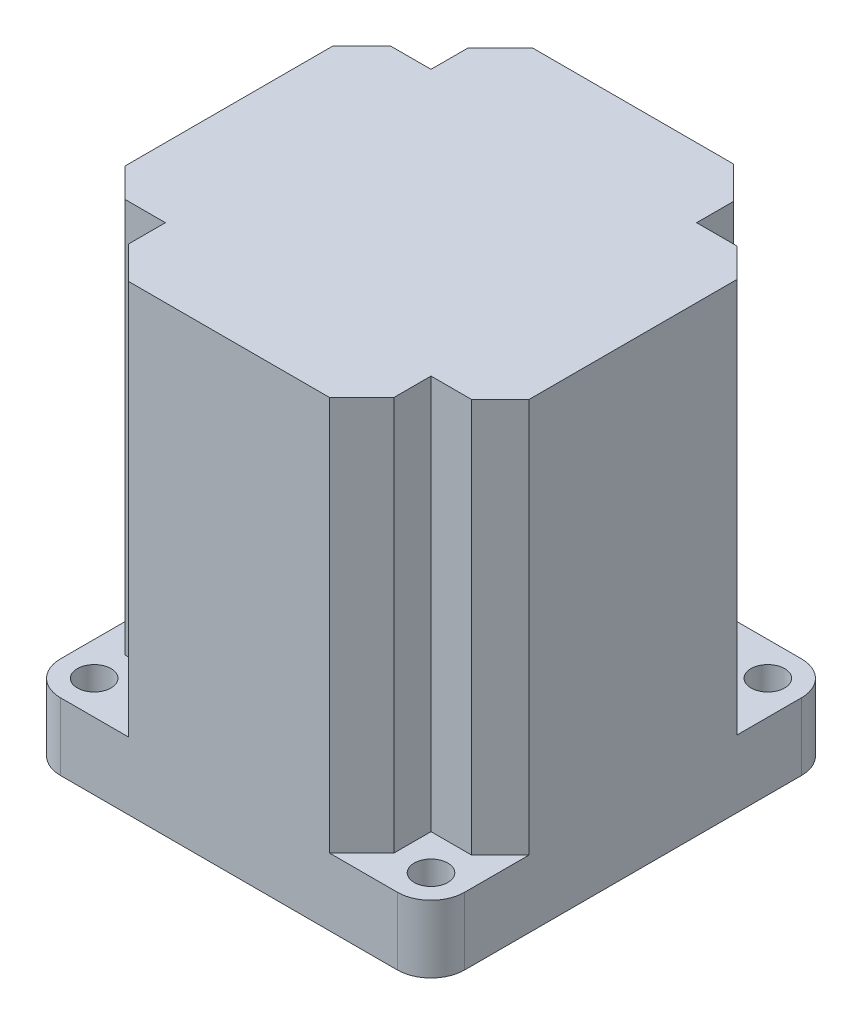
SolidWorks part; units mm, degrees
material "ABS"
ref_plane "Front Plane" through (0, 0, 0) normal (0, 0, 1) x (1, 0, 0)
ref_plane "Top Plane" through (0, 0, 0) normal (0, 1, 0) x (1, 0, 0)
ref_plane "Right Plane" through (0, 0, 0) normal (1, 0, 0) x (0, 0, -1)
sketch "Sketch1" plane through (0, 0, 0) normal (0, 1, 0) x (1, 0, 0)
  line L0 (0, 0) -> (-21, 0) construction
  line L1 (17.5, -21) -> (-17.5, -21)
  line L2 (21, -17.5) -> (21, 17.5)
  line L3 (17.5, 21) -> (-17.5, 21)
  line L4 (-21, -17.5) -> (-21, 17.5)
  line L5 (21, -21) -> (-21, 21) construction
  line L6 (21, 21) -> (-21, -21) construction
  line L7 (0, 0) -> (0, 21) construction
  arc A0 (21, 17.5) -> (17.5, 21) centre (17.5, 17.5) ccw
  arc A1 (21, -17.5) -> (17.5, -21) centre (17.5, -17.5) cw
  arc A2 (-17.5, -21) -> (-21, -17.5) centre (-17.5, -17.5) cw
  arc A3 (-21, 17.5) -> (-17.5, 21) centre (-17.5, 17.5) cw
  circle A4 centre (-17.5, -17.5) radius 1.75
  circle A5 centre (-17.5, 17.5) radius 1.75
  circle A6 centre (17.5, -17.5) radius 1.75
  circle A7 centre (17.5, 17.5) radius 1.75
  circle A8 centre (0, 0) radius 14
  point P0 (0, 0)
  dimension "D3" = 3.5
  dimension "D4" = 3.5
  dimension "D5" = 28
  dimension "D1" = 42
  dimension "D2" = 42
extrude "Boss-Extrude1" add sketch "Sketch1" along normal blind 7
sketch "Sketch2" plane through (0, 7, 0) normal (0, 1, 0) x (1, 0, 0)
  line L0 (21, -17.5) -> (21, 17.5) construction
  line L1 (-17.5, -21) -> (17.5, -21) construction
  line L2 (-21, 17.5) -> (-21, -17.5) construction
  line L3 (17.5, 21) -> (-17.5, 21) construction
  line L4 (21, -17.5) -> (21, 17.5)
  line L5 (-17.5, -21) -> (17.5, -21)
  line L6 (-21, 17.5) -> (-21, -17.5)
  line L7 (17.5, 21) -> (-17.5, 21)
  arc A0 (21, 17.5) -> (17.5, 21) centre (17.5, 17.5) ccw construction
  arc A1 (17.5, -21) -> (21, -17.5) centre (17.5, -17.5) ccw construction
  arc A2 (-21, -17.5) -> (-17.5, -21) centre (-17.5, -17.5) ccw construction
  arc A3 (-17.5, 21) -> (-21, 17.5) centre (-17.5, 17.5) ccw construction
  arc A4 (21, 17.5) -> (17.5, 21) centre (17.5, 17.5) ccw
  arc A5 (17.5, -21) -> (21, -17.5) centre (17.5, -17.5) ccw
  arc A6 (-21, -17.5) -> (-17.5, -21) centre (-17.5, -17.5) ccw
  arc A7 (-17.5, 21) -> (-21, 17.5) centre (-17.5, 17.5) ccw
extrude "Boss-Extrude2" add sketch "Sketch2" along normal blind 34
sketch "Sketch3" plane through (0, 41, 0) normal (0, 1, 0) x (1, 0, 0)
  line L4 (17.5, 21) -> (-17.5, 21)
  line L5 (-21, 17.5) -> (-21, -17.5)
  line L6 (-17.5, -21) -> (17.5, -21)
  line L7 (21, -17.5) -> (21, 17.5)
  line L8 (17.5, 21) -> (-17.5, 21)
  line L9 (-21, 17.5) -> (-21, -17.5)
  line L10 (-17.5, -21) -> (17.5, -21)
  line L11 (21, -17.5) -> (21, 17.5)
  arc A4 (21, 17.5) -> (17.5, 21) centre (17.5, 17.5) ccw
  arc A5 (-17.5, 21) -> (-21, 17.5) centre (-17.5, 17.5) ccw
  arc A6 (-21, -17.5) -> (-17.5, -21) centre (-17.5, -17.5) ccw
  arc A7 (17.5, -21) -> (21, -17.5) centre (17.5, -17.5) ccw
  arc A8 (21, 17.5) -> (17.5, 21) centre (17.5, 17.5) ccw
  arc A9 (-17.5, 21) -> (-21, 17.5) centre (-17.5, 17.5) ccw
  arc A10 (-21, -17.5) -> (-17.5, -21) centre (-17.5, -17.5) ccw
  arc A11 (17.5, -21) -> (21, -17.5) centre (17.5, -17.5) ccw
  dimension "D1" = 0
extrude "Boss-Extrude3" add sketch "Sketch3" along normal blind 7
sketch "Sketch4" plane through (0, 48, 0) normal (0, 1, 0) x (1, 0, 0)
  line L0 (-13.8, 13.8) -> (-18, 13.8)
  line L1 (-13.8, 13.8) -> (-13.8, 17.65)
  line L2 (-18, 13.8) -> (-21, 10.8)
  line L3 (-13.8, 17.65) -> (-10.45, 21)
  line L4 (17.5, 21) -> (-17.5, 21)
  line L5 (-21, 17.5) -> (-21, -17.5)
  line L6 (-17.5, -21) -> (17.5, -21)
  line L7 (21, -17.5) -> (21, 17.5)
  line L8 (17.5, 21) -> (10.45, 21)
  line L9 (-21, 17.5) -> (-21, 10.8)
  line L10 (-17.5, -21) -> (-10.45, -21)
  line L11 (21, -17.5) -> (21, -10.8)
  line L12 (-17.5, 17.5) -> (0, 0) construction
  line L13 (0, 0) -> (-30, 0) construction
  line L14 (0, 0) -> (0, 25) construction
  line L15 (-17.5, -17.5) -> (0, 0) construction
  line L16 (-18, -13.8) -> (-21, -10.8)
  line L17 (-13.8, -13.8) -> (-18, -13.8)
  line L18 (-13.8, -13.8) -> (-13.8, -17.65)
  line L19 (-13.8, -17.65) -> (-10.45, -21)
  line L20 (17.5, -17.5) -> (0, 0) construction
  line L21 (18, -13.8) -> (21, -10.8)
  line L22 (13.8, -13.8) -> (18, -13.8)
  line L23 (13.8, -13.8) -> (13.8, -17.65)
  line L24 (13.8, -17.65) -> (10.45, -21)
  line L25 (17.5, 17.5) -> (0, 0) construction
  line L26 (18, 13.8) -> (21, 10.8)
  line L27 (13.8, 13.8) -> (18, 13.8)
  line L28 (13.8, 13.8) -> (13.8, 17.65)
  line L29 (13.8, 17.65) -> (10.45, 21)
  line L30 (-10.45, 21) -> (-17.5, 21)
  line L31 (-21, -10.8) -> (-21, -17.5)
  line L32 (10.45, -21) -> (17.5, -21)
  line L33 (21, 10.8) -> (21, 17.5)
  arc A4 (21, 17.5) -> (17.5, 21) centre (17.5, 17.5) ccw
  arc A5 (-17.5, 21) -> (-21, 17.5) centre (-17.5, 17.5) ccw
  arc A6 (-21, -17.5) -> (-17.5, -21) centre (-17.5, -17.5) ccw
  arc A7 (17.5, -21) -> (21, -17.5) centre (17.5, -17.5) ccw
  arc A8 (21, 17.5) -> (17.5, 21) centre (17.5, 17.5) ccw
  arc A9 (-17.5, 21) -> (-21, 17.5) centre (-17.5, 17.5) ccw
  arc A10 (-21, -17.5) -> (-17.5, -21) centre (-17.5, -17.5) ccw
  arc A11 (17.5, -21) -> (21, -17.5) centre (17.5, -17.5) ccw
  dimension "D3" = 45
  dimension "D4" = 45
  dimension "D5" = 4.2
  dimension "D6" = 3.85
  dimension "D7" = 3
  dimension "D1" = 0
extrude "Cut-Extrude1" cut sketch "Sketch4" against normal blind 41
extrude "Cut-Extrude2" cut sketch "Sketch1<2>" along normal blind 15 contours A8 region at (0, 0, 0)
sketch "Sketch1<2>" plane through (0, 0, 0) normal (0, 1, 0) x (1, 0, 0) same geometry as "Sketch1"
